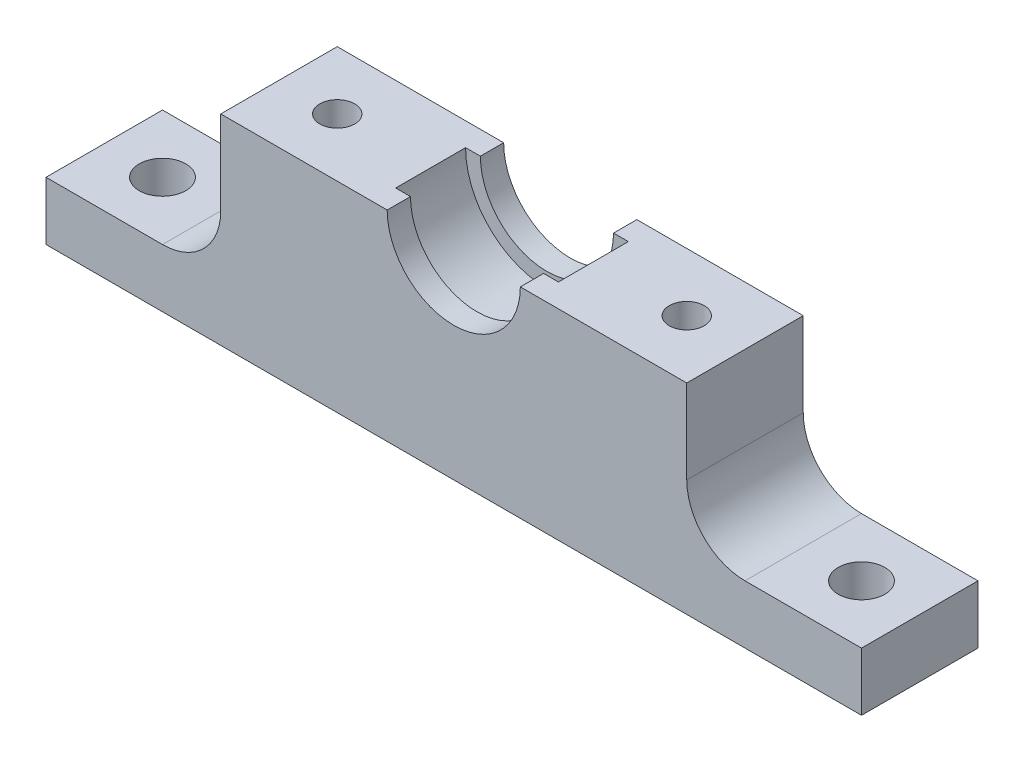
SolidWorks part; units mm, degrees
ref_plane "Front Plane" through (0, 0, 0) normal (0, 0, 1) x (1, 0, 0)
ref_plane "Top Plane" through (0, 0, 0) normal (0, 1, 0) x (1, 0, 0)
ref_plane "Right Plane" through (0, 0, 0) normal (1, 0, 0) x (0, 0, -1)
sketch "Sketch1" plane through (0, 0, 0) normal (0, 1, 0) x (1, 0, 0)
  line L1 (20, -5) -> (-20, -5)
  line L2 (20, -5) -> (20, 5)
  line L3 (20, 5) -> (-20, 5)
  line L4 (-20, -5) -> (-20, 5)
  line L5 (20, -5) -> (-20, 5) construction
  line L6 (20, 5) -> (-20, -5) construction
  point P0 (0, 0)
  dimension "D1" = 40
  dimension "D2" = 10
extrude "Boss-Extrude1" add sketch "Sketch1" along normal blind 17.2098
ref_plane "Plane2" through (0, 0, 0) normal (0, 0, -1) x (-1, 0, 0)
sketch "Sketch2" plane through (0, 0, 0) normal (0, 0, -1) x (-1, 0, 0)
  line L0 (-20, 17.2098) -> (20, 17.2098) construction
  line L1 (-6.985, 17.2098) -> (6.985, 17.2098)
  arc A0 (-6.985, 17.2098) -> (6.985, 17.2098) centre (0, 17.2098) ccw
  dimension "D1" = 13.97
extrude "Cut-Extrude1" cut sketch "Sketch2" against normal mid plane 6
sketch "Sketch3" plane through (0, 0, 0) normal (0, 0, -1) x (-1, 0, 0)
  line L0 (-20, 17.2098) -> (20, 17.2098) construction
  line L1 (-5.715, 17.2098) -> (5.715, 17.2098)
  arc A0 (-5.715, 17.2098) -> (5.715, 17.2098) centre (0, 17.2098) ccw
  dimension "D1" = 11.43
extrude "Cut-Extrude2" cut sketch "Sketch3" against normal mid plane 10
sketch "Sketch4" plane through (0, 17.2098, 0) normal (0, 1, 0) x (1, 0, 0)
  line L0 (0, -5) -> (0, 5) construction
  line L1 (5.715, 5) -> (-5.715, 5) construction
  line L2 (20, -5) -> (20, 5) construction
  circle A0 centre (15, 0) radius 1.5
  circle A1 centre (-15, 0) radius 1.5
  point P6 (0, 0)
  point P12 (20, 0)
  dimension "D1" = 3
  dimension "D2" = 5
extrude "Cut-Extrude3" cut sketch "Sketch4" against normal blind 7
sketch "Sketch5" plane through (0, 0, 0) normal (0, -1, 0) x (1, 0, 0)
  line L0 (-20, -5) -> (-20, 5) construction
  line L1 (-35, 5) -> (-20, 5)
  line L2 (-35, 5) -> (-35, -5)
  line L3 (-35, -5) -> (-20, -5)
  line L4 (-20, 5) -> (-20, -5)
  line L5 (-35, 5) -> (-20, -5) construction
  line L6 (-35, -5) -> (-20, 5) construction
  line L7 (20, -5) -> (-20, -5) construction
  line L8 (-20, 5) -> (20, 5) construction
  line L9 (0, -5) -> (0, 5) construction
  line L10 (35, -5) -> (20, -5)
  line L11 (20, 5) -> (20, -5)
  line L12 (35, 5) -> (20, 5)
  line L13 (35, 5) -> (35, -5)
  circle A0 centre (-30, 0) radius 2
  circle A1 centre (30, 0) radius 2
  point P0 (-27.5, 0)
  point P15 (0, 0)
  dimension "D1" = 4
  dimension "D2" = 15
  dimension "D3" = 5
extrude "Boss-Extrude2" add sketch "Sketch5" against normal blind 5
fillet "Fillet1" radius 5 2 edges at (-20, 5, 0) (20, 5, 0)
